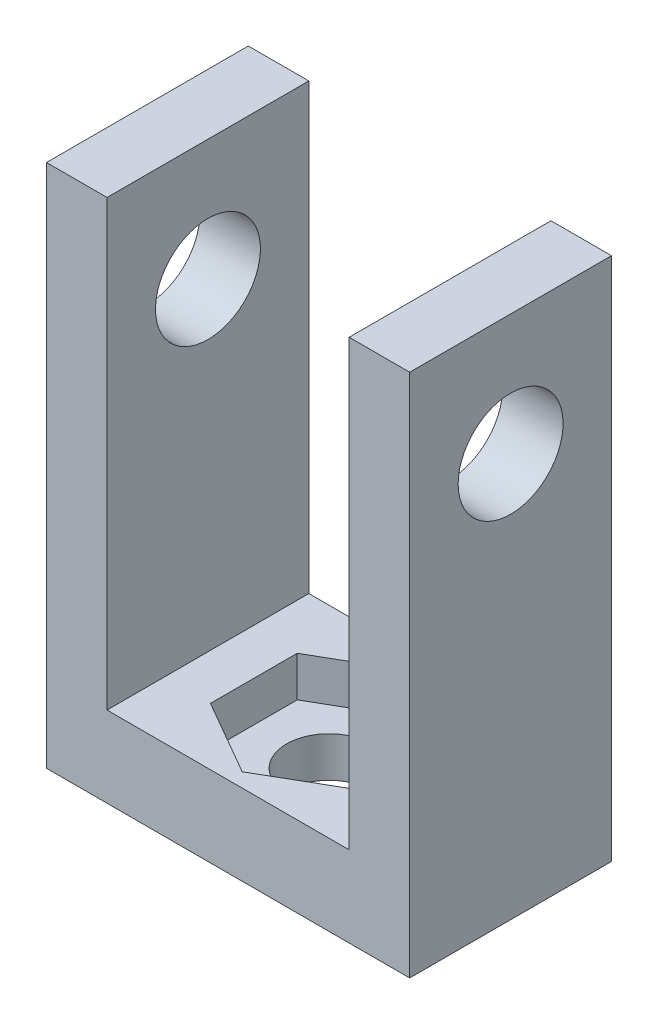
SolidWorks part; units mm, degrees
ref_plane "Front Plane" through (0, 0, 0) normal (0, 0, 1) x (1, 0, 0)
ref_plane "Top Plane" through (0, 0, 0) normal (0, 1, 0) x (1, 0, 0)
ref_plane "Right Plane" through (0, 0, 0) normal (1, 0, 0) x (0, 0, -1)
sketch "Sketch1" plane through (0, 0, 0) normal (0, 0, 1) x (1, 0, 0)
  line L0 (-6, 0) -> (6, 0)
  line L1 (-6, 0) -> (-6, 22)
  line L2 (6, 0) -> (6, 22)
  line L3 (9, -3) -> (9, 22)
  line L4 (-9, -3) -> (9, -3)
  line L5 (-9, -3) -> (-9, 22)
  line L6 (6, 22) -> (9, 22)
  line L7 (-6, 22) -> (-9, 22)
  point P4 (0, 0)
  dimension "D1" = 12
  dimension "D2" = 22
  dimension "D3" = 3
extrude "Boss-Extrude1" add sketch "Sketch1" along normal blind 10
sketch "Sketch2" plane through (-9, 0, 0) normal (-1, 0, 0) x (0, 0, 1)
  line L0 (5, 16) -> (5, 22)
  line L1 (10, 22) -> (0, 22) construction
  circle A0 centre (5, 16) radius 2.6
  dimension "D1" = 5.2
  dimension "D2" = 6
extrude "Cut-Extrude4" cut sketch "Sketch2" against normal blind 25 contours A0 region at (-9, 14.2135, 3.2135)
sketch "Sketch5" plane through (0, -3, 0) normal (0, -1, 0) x (1, 0, 0)
  line L0 (-9, 5) -> (9, 5)
  line L1 (-9, 10) -> (-9, 0) construction
  line L2 (9, 10) -> (9, 0) construction
  line L3 (0, 10) -> (0, 5)
  line L4 (-9, 10) -> (9, 10) construction
  circle A0 centre (0, 5) radius 2.1
  dimension "D1" = 4.2
extrude "Cut-Extrude5" cut sketch "Sketch5" against normal blind 10 contours L0 A0 | L0 A0 L3 | L3 A0 L0 region at (0.8913, -3, 5.8913) region at (0, -3, 4.1087) region at (-0.8913, -3, 5.8913)
sketch "Sketch6" plane through (0, 0, 0) normal (0, 1, 0) x (1, 0, 0)
  circle A0 centre (0, -5) radius 4.5
  dimension "D1" = 9
extrude "Cut-Extrude6" cut sketch "Sketch6" against normal blind 2
sketch "Sketch7" plane through (0, -3, 0) normal (0, -1, 0) x (1, 0, 0)
  line L4 (-9, 0) -> (9, 0)
  line L5 (9, 0) -> (9, 10)
  line L6 (9, 10) -> (-9, 10)
  line L7 (-9, 10) -> (-9, 0)
  line L8 (-9, 0) -> (9, 0)
  line L9 (9, 0) -> (9, 10)
  line L10 (9, 10) -> (-9, 10)
  line L11 (-9, 10) -> (-9, 0)
  circle A0 centre (0, 5) radius 2.1 construction
  circle A1 centre (0, 5) radius 2.1
  dimension "D1" = 0
extrude "Boss-Extrude2" add sketch "Sketch7" along normal blind 1
sketch "Sketch8" plane through (0, 0, 0) normal (0, 1, 0) x (1, 0, 0)
  line L0 (0, -0.5) -> (0, -0.7)
  line L2 (0, -0.7) -> (-3.7239, -2.85)
  line L3 (-3.7239, -2.85) -> (-3.7239, -7.15)
  line L4 (6, 0) -> (-6, 0)
  line L5 (-6, 0) -> (-6, -10)
  line L6 (-6, -10) -> (6, -10)
  line L7 (6, -10) -> (6, 0)
  line L8 (6, 0) -> (-6, 0)
  line L9 (-6, 0) -> (-6, -10)
  line L10 (-6, -10) -> (6, -10)
  line L11 (6, -10) -> (6, 0)
  line L12 (-3.7239, -7.15) -> (0, -9.3)
  line L13 (0, -9.3) -> (3.7239, -7.15)
  line L14 (3.7239, -7.15) -> (3.7239, -2.85)
  line L15 (3.7239, -2.85) -> (0, -0.7)
  circle A0 centre (0, -5) radius 4.5 construction
  circle A1 centre (0, -5) radius 4.5
  circle A2 centre (0, -5) radius 3.7239 construction
  circle M6 centre (0, -5) radius 4.5
  dimension "D2" = 0.2
  dimension "D1" = 0
extrude "Boss-Extrude3" add sketch "Sketch8" against normal up to surface (2 mm away) contours L15 L14 L13 L12 L3 L2 M6 region at (3.092, 0, 1.908) up to face at (-4.5, -2, 5)
